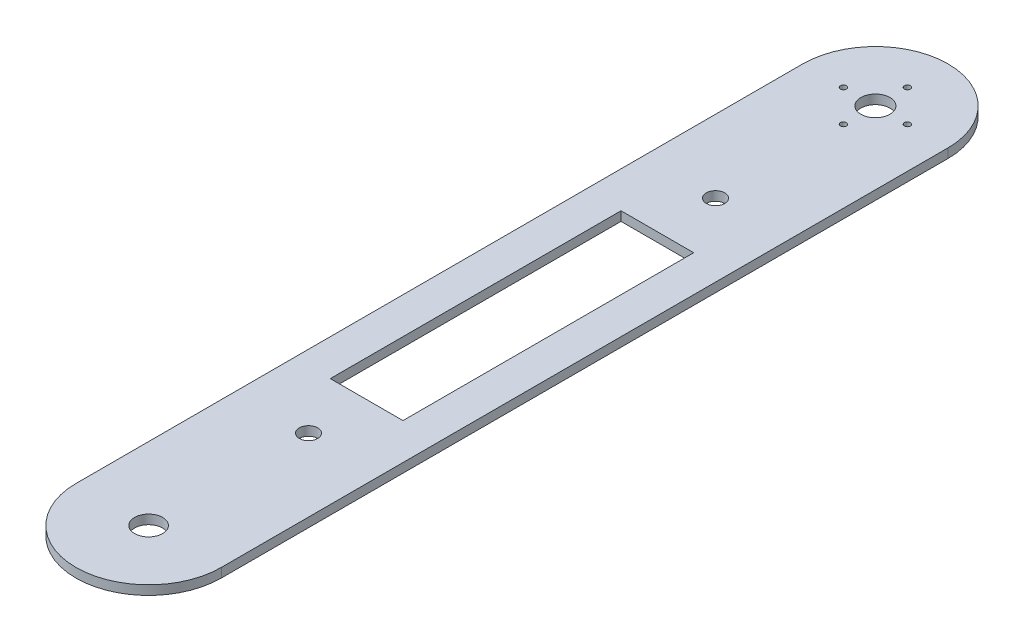
SolidWorks part; units mm, degrees
ref_plane "Front" through (0, 0, 0) normal (0, 0, 1) x (1, 0, 0)
ref_plane "Top" through (0, 0, 0) normal (0, 1, 0) x (1, 0, 0)
ref_plane "Right" through (0, 0, 0) normal (1, 0, 0) x (0, 0, -1)
sketch "Sketch1" plane through (0, 0, 0) normal (0, 1, 0) x (1, 0, 0)
  line L1 (0, 0) -> (50, 0)
  line L2 (0, 0) -> (0, -300)
  line L3 (0, -300) -> (50, -300)
  line L4 (50, 0) -> (50, -300)
  dimension "D1" = 300
  dimension "D2" = 50
extrude "Boss-Extrude1" add sketch "Sketch1" along normal blind 3.175
sketch "Sketch2" plane through (0, 3.175, 0) normal (0, 1, 0) x (1, 0, 0)
  line L0 (0, -25) -> (0, 0)
  line L1 (0, 0) -> (50, 0)
  line L2 (50, 0) -> (50, -25)
  line L3 (0, -275) -> (0, -300)
  line L4 (0, -300) -> (50, -300)
  line L5 (50, -300) -> (50, -275)
  circle A0 centre (25, -25) radius 25
  circle A1 centre (25, -275) radius 25
  line M1 (0, 0) -> (0, -300)
  line M2 (0, -300) -> (50, -300)
  line M3 (50, -300) -> (50, 0)
  line M4 (50, 0) -> (0, 0)
extrude "Cut-Extrude1" cut sketch "Sketch2" against normal blind 6.35 contours A0 M3 M4 | A0 L1 M1 | A1 L4 M3 | A1 M1 M2 region at (5.5842, 3.175, 5.5842) region at (44.4158, 3.175, 5.5842) region at (5.5842, 3.175, 294.4158) region at (44.4158, 3.175, 294.4158)
sketch "Sketch3" plane through (0, 3.175, 0) normal (0, 1, 0) x (1, 0, 0)
  line L0 (25, 0) -> (25, -300) construction
  line L1 (0, -25) -> (50, -25) construction
  arc A0 (50, -25) -> (0, -25) centre (25, -25) ccw construction
  circle A1 centre (25, -25) radius 5
  circle A2 centre (25, -275) radius 4.82
  circle A3 centre (25, -14) radius 1.025
  circle A4 centre (14, -25) radius 1.025
  circle A5 centre (25, -36) radius 1.025
  circle A6 centre (36, -25) radius 1.025
  arc A7 (0, -275) -> (50, -275) centre (25, -275) ccw construction
  dimension "D1" = 2.05
  dimension "D2" = 9.64
  dimension "D3" = 10
  dimension "D4" = 11
  dimension "D6" = 11
  dimension "D7" = 11
  dimension "D5" = 11
extrude "Cut-Extrude2" cut sketch "Sketch3" against normal blind 6.35
sketch "Sketch4" plane through (0, 3.175, 0) normal (0, 1, 0) x (1, 0, 0)
  line L0 (25, 0) -> (25, -300) construction
  line L1 (0, -150) -> (50, -150) construction
  line L2 (12.5, -100) -> (37.5, -100)
  line L3 (12.5, -100) -> (12.5, -200)
  line L4 (12.5, -200) -> (37.5, -200)
  line L5 (37.5, -100) -> (37.5, -200)
  line L6 (0, -25) -> (0, -275) construction
  line L7 (50, -275) -> (50, -25) construction
  circle A0 centre (25, -80) radius 3.175
  circle A1 centre (25, -220) radius 3.175
  arc A2 (50, -25) -> (0, -25) centre (25, -25) ccw construction
  arc A3 (0, -275) -> (50, -275) centre (25, -275) ccw construction
  dimension "D3" = 6.35
  dimension "D4" = 70
  dimension "D1" = 25
  dimension "D2" = 100
extrude "Cut-Extrude3" cut sketch "Sketch4" against normal blind 6.35
